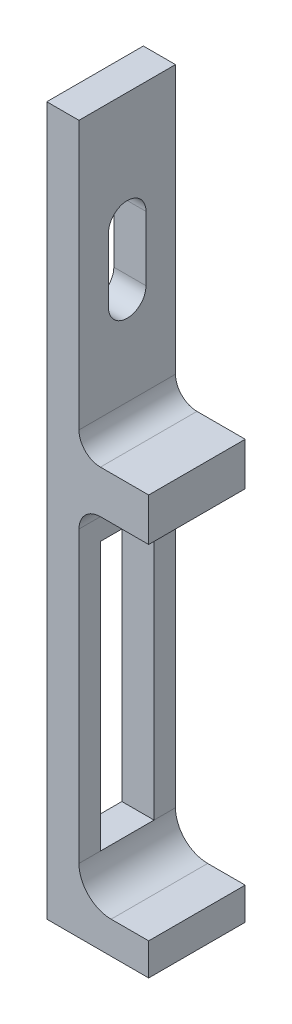
SolidWorks part; units mm, degrees
material "ПВХ Жесткий"
ref_plane "Спереди" through (0, 0, 0) normal (0, 0, 1) x (1, 0, 0)
ref_plane "Сверху" through (0, 0, 0) normal (0, 1, 0) x (1, 0, 0)
ref_plane "Справа" through (0, 0, 0) normal (1, 0, 0) x (0, 0, -1)
sketch "Эскиз1" plane through (0, 0, 0) normal (0, 0, 1) x (1, 0, 0)
  line L0 (0, 0) -> (9.5, 0)
  line L1 (9.5, 0) -> (9.5, 3)
  line L2 (9.5, 3) -> (3, 3)
  line L3 (3, 3) -> (3, 66)
  line L4 (3, 66) -> (0, 66)
  line L5 (0, 66) -> (0, 0)
  dimension "D1" = 3
  dimension "D2" = 66
  dimension "D3" = 9.5
extrude "Бобышка-Вытянуть1" add sketch "Эскиз1" along normal blind 9
sketch "Эскиз2" plane through (3, 0, 0) normal (1, 0, 0) x (0, 0, -1)
  line L0 (-4.5, 66) -> (-4.5, 3) construction
  line L1 (-9, 66) -> (0, 66) construction
  line L2 (-9, 3) -> (0, 3) construction
ref_plane "Плоскость1" through (0, 0, 4.5) normal (0, 0, 1) x (0, -1, 0)
sketch "Эскиз3" plane through (0, 0, 0) normal (-1, 0, 0) x (0, 0, 1)
  line L0 (9, 66) -> (0, 66) construction
  line L1 (4.5, 66) -> (4.5, 3) construction
  line L2 (4.5, 66) -> (4.5, 3) construction
  circle A1 centre (4.5, 52.52) radius 1.75
  dimension "D1" = 13.48
  dimension "D2" = 3.5
sketch "Эскиз4" plane through (0, 0, 0) normal (-1, 0, 0) x (0, 0, 1)
  line L0 (4.5, 55.52) -> (4.5, 49.52) construction
  line L1 (6.25, 55.52) -> (6.25, 49.52)
  line L2 (2.75, 55.52) -> (2.75, 49.52)
  line L3 (4.5, 66) -> (4.5, 43.3234) construction
  line L4 (9, 66) -> (0, 66) construction
  circle A0 centre (4.5, 52.52) radius 1.75 construction
  circle A1 centre (4.5, 52.52) radius 1.75 construction
  arc A2 (6.25, 55.52) -> (2.75, 55.52) centre (4.5, 55.52) ccw
  arc A3 (2.75, 49.52) -> (6.25, 49.52) centre (4.5, 49.52) ccw
  point P5 (4.5, 52.52)
  dimension "D1" = 6
extrude "Вырез-Вытянуть2" cut sketch "Эскиз4" against normal through all
sketch "Эскиз5" plane through (0, 0, 9) normal (0, 0, 1) x (1, 0, 0)
  line L0 (3, 3) -> (3, 66) construction
  line L1 (9.5, 3) -> (3, 3) construction
  line L2 (3, 3) -> (3, 10)
  line L3 (9.5, 3) -> (3, 3)
  line L4 (9.5, 3) -> (3, 10)
  dimension "D1" = 7
sketch "Эскиз6" plane through (3, 0, 0) normal (1, 0, 0) x (0, 0, -1)
  line L0 (-7, 31) -> (-2, 31)
  line L1 (-7, 31) -> (-7, 6)
  line L2 (-2, 31) -> (-2, 6)
  line L3 (-7, 6) -> (-2, 6)
  line L4 (-4.5, 31) -> (-4.5, 6) construction
  line L5 (-4.5, 66) -> (-4.5, 3) construction
  line L6 (-9, 3) -> (-9, 66) construction
  line L7 (-9, 3) -> (0, 3) construction
  dimension "D1" = 2
  dimension "D2" = 25
  dimension "D3" = 3
extrude "Вырез-Вытянуть3" cut sketch "Эскиз6" against normal through all
fillet "Скругление1" radius 3 1 edges at (3, 3, 4.5)
sketch "Эскиз7" plane through (0, 0, 9) normal (0, 0, 1) x (1, 0, 0)
  line L0 (3, 39) -> (3, 35)
  line L1 (3, 39) -> (9.5, 39)
  line L2 (3, 35) -> (9.5, 35)
  line L3 (9.5, 39) -> (9.5, 35)
  line L4 (3, 6) -> (3, 66) construction
  line L5 (0, 0) -> (9.5, 0) construction
  line L6 (9.5, 0) -> (9.5, 3) construction
  dimension "D1" = 4
  dimension "D2" = 35
extrude "Бобышка-Вытянуть2" add sketch "Эскиз7" against normal up to surface (9 mm away) up to face at (4.3398, 20.4827, 0)
fillet "Скругление2" radius 2 2 edges at (3, 35, 4.5) (3, 39, 4.5)
